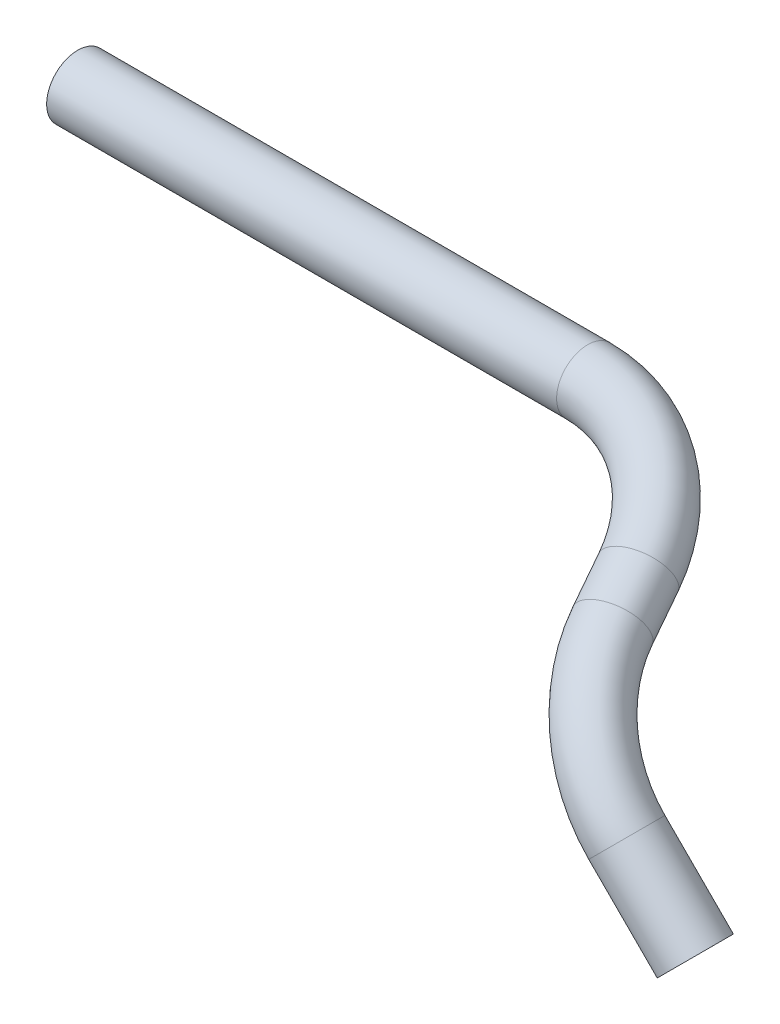
SolidWorks part; units mm, degrees
ref_plane "Front Plane" through (0, 0, 0) normal (0, 0, 1) x (1, 0, 0)
ref_plane "Top Plane" through (0, 0, 0) normal (0, 1, 0) x (1, 0, 0)
ref_plane "Right Plane" through (0, 0, 0) normal (1, 0, 0) x (0, 0, -1)
sketch3d "3DSketch1"
  line L0 (0, 0, 0) -> (38.1845, -38.1845, 0) construction
  line L1 (0, 0, 0) -> (35.8649, 0, 0) construction
  line L2 (0, 0, 0) -> (-27.9578, 27.9578, 0)
  line L3 (-65.4486, 68.2382, -31.6887) -> (-71.4853, 75.7309, -48.2267)
  line L4 (-131.742, 93.668, -87.8182) -> (-339.9371, 93.668, -87.8182)
  arc A0 (-71.4853, 75.7309, -48.2267) -> (-131.742, 93.668, -87.8182) centre (-131.742, 67.463, -29.9775) ccw
  arc A1 (-27.9578, 27.9578, 0) -> (-65.4486, 68.2382, -31.6887) centre (-25.1681, 30.7474, -63.3773) ccw
  point P8 (0, 0, 0)
  point P11 (-85.9371, 93.668, -87.8182)
  point P12 (-131.742, 125.3037, -3.7725)
  point P15 (-53.8815, 53.8815, 0)
  point P16 (-69.9827, -14.0671, -67.3225)
  point P17 (-53.8815, 53.8815, 0)
  point P18 (-147.7698, 113.5612, -131.7273)
  dimension "D5" = 63.5
  dimension "D1" = 45
  dimension "D2" = 76.2
  dimension "D3" = 101.6
  dimension "D4" = 254
  dimension "D6" = 120
sweep "Sweep1" add path "3DSketch1" circular profile diameter 25.4 parameters "D3"=25.4
